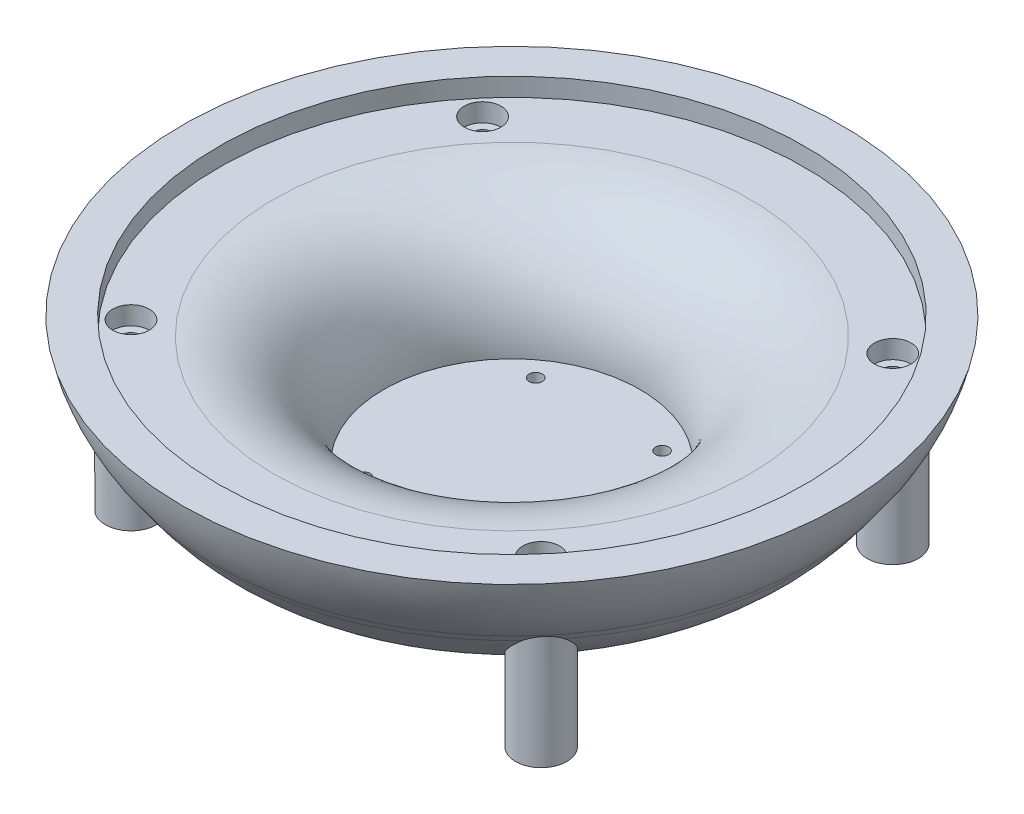
SolidWorks part; units mm, degrees
ref_plane "Front Plane" through (0, 0, 0) normal (0, 0, 1) x (1, 0, 0)
ref_plane "Top Plane" through (0, 0, 0) normal (0, 1, 0) x (1, 0, 0)
ref_plane "Right Plane" through (0, 0, 0) normal (1, 0, 0) x (0, 0, -1)
sketch "Sketch3" plane through (0, 0, 0) normal (0, 1, 0) x (1, 0, 0)
  circle A0 centre (0, 0) radius 90
extrude "Boss-Extrude2" add sketch "Sketch3" along normal blind 10
sketch "Sketch4" plane through (0, 10, 0) normal (0, 1, 0) x (1, 0, 0)
  circle A0 centre (0, 0) radius 80
extrude "Cut-Extrude1" cut sketch "Sketch4" against normal blind 5
sketch "Sketch14" plane through (0, 0, 0) normal (0, -1, 0) x (1, 0, 0)
  circle A0 centre (56, 48) radius 7
extrude "Boss-Extrude6" add sketch "Sketch14" along normal blind 40
sketch "Sketch15" plane through (0, 5, 0) normal (0, 1, 0) x (1, 0, 0)
  circle A0 centre (56, -48) radius 5
  point P2 (0, 0)
extrude "Cut-Extrude4" cut sketch "Sketch15" against normal blind 5
sketch "Sketch16" plane through (0, -40, 0) normal (0, -1, 0) x (1, 0, 0)
  circle A0 centre (56, 48) radius 4
extrude "Cut-Extrude5" cut sketch "Sketch16" against normal blind 32
sketch "Sketch17" plane through (0, -8, 0) normal (0, -1, 0) x (1, 0, 0)
  circle A0 centre (56, 48) radius 2.8
extrude "Cut-Extrude6" cut sketch "Sketch17" against normal through all
sketch "Sketch20" plane through (0, 0, 0) normal (0, -1, 0) x (1, 0, 0)
  circle A0 centre (56, -48) radius 7.0017
extrude "Boss-Extrude7" add sketch "Sketch20" along normal blind 40
sketch "Sketch22" plane through (0, -40, 0) normal (0, -1, 0) x (1, 0, 0)
  circle A0 centre (56, -48) radius 3.75
extrude "Cut-Extrude8" cut sketch "Sketch22" against normal blind 32
sketch "Sketch23" plane through (0, -8, 0) normal (0, -1, 0) x (1, 0, 0)
  circle A0 centre (56, -48) radius 2.75
extrude "Cut-Extrude9" cut sketch "Sketch23" against normal through all
sketch "Sketch24" plane through (0, 0, 0) normal (0, -1, 0) x (1, 0, 0)
  circle A0 centre (-56, 48) radius 7
extrude "Boss-Extrude8" add sketch "Sketch24" along normal blind 40
sketch "Sketch25" plane through (0, 5, 0) normal (0, 1, 0) x (1, 0, 0)
  circle A0 centre (-56, -48) radius 5
extrude "Cut-Extrude10" cut sketch "Sketch25" against normal blind 5
sketch "Sketch26" plane through (0, -40, 0) normal (0, -1, 0) x (1, 0, 0)
  circle A0 centre (-56, 48) radius 3.75
extrude "Cut-Extrude11" cut sketch "Sketch26" against normal blind 32
sketch "Sketch27" plane through (0, -8, 0) normal (0, -1, 0) x (1, 0, 0)
  circle A0 centre (-56, 48) radius 2.75
extrude "Cut-Extrude12" cut sketch "Sketch27" against normal through all
sketch "Sketch28" plane through (0, 0, 0) normal (0, -1, 0) x (1, 0, 0)
  circle A0 centre (-56, -48) radius 7
extrude "Boss-Extrude9" add sketch "Sketch28" along normal blind 40
sketch "Sketch29" plane through (0, 5, 0) normal (0, 1, 0) x (1, 0, 0)
  circle A0 centre (-56, 48) radius 5
extrude "Cut-Extrude13" cut sketch "Sketch29" against normal blind 5
sketch "Sketch30" plane through (0, -40, 0) normal (0, -1, 0) x (-1, 0, 0)
  circle A0 centre (56, 48) radius 3.75
extrude "Cut-Extrude14" cut sketch "Sketch30" against normal blind 32
sketch "Sketch31" plane through (0, -8, 0) normal (0, -1, 0) x (1, 0, 0)
  circle A0 centre (-56, -48) radius 2.75
extrude "Cut-Extrude15" cut sketch "Sketch31" against normal through all
sketch "Sketch32" plane through (0, 5, 0) normal (0, 1, 0) x (1, 0, 0)
  circle A0 centre (56, 48) radius 5
extrude "Cut-Extrude16" cut sketch "Sketch32" against normal blind 5
sketch "Sketch35" plane through (0, 0, 0) normal (0, -1, 0) x (1, 0, 0)
  circle A0 centre (0, 0) radius 85
extrude "Boss-Extrude11" add sketch "Sketch35" along normal blind 30
sketch "Sketch38" plane through (0, 5, 0) normal (0, 1, 0) x (1, 0, 0)
  circle A0 centre (0, 0) radius 35
extrude "Cut-Extrude18" cut sketch "Sketch38" against normal blind 30
sketch "Sketch39" plane through (0, -25, 0) normal (0, 1, 0) x (1, 0, 0)
  circle A0 centre (17.5, 23.5) radius 1.8
extrude "Cut-Extrude19" cut sketch "Sketch39" against normal through all
sketch "Sketch40" plane through (0, -25, 0) normal (0, 1, 0) x (1, 0, 0)
  circle A0 centre (17.5, -23.5) radius 1.8
extrude "Cut-Extrude20" cut sketch "Sketch40" against normal through all
sketch "Sketch41" plane through (0, -30, 0) normal (0, -1, 0) x (1, 0, 0)
  circle A0 centre (-17, 23.5) radius 1.8
extrude "Cut-Extrude21" cut sketch "Sketch41" against normal through all
sketch "Sketch43" plane through (0, -30, 0) normal (0, -1, 0) x (1, 0, 0)
  circle A0 centre (-17, -23.5) radius 1.8
extrude "Cut-Extrude22" cut sketch "Sketch43" against normal through all
fillet "Fillet12" radius 45 1 edges at (0, -30, -85)
fillet "Fillet13" radius 45 1 edges at (0, 0, 85)
fillet "Fillet14" radius 45 1 edges at (0, 0, 90)
fillet "Fillet15" radius 30 1 edges at (0, 5, 35)
sketch "Sketch44" plane through (0, -30, 0) normal (0, -1, 0) x (1, 0, 0)
  circle A0 centre (-56, 48) radius 3.75
extrude "Cut-Extrude23" cut sketch "Sketch44" against normal blind 27
sketch "Sketch45" plane through (0, -3, 0) normal (0, -1, 0) x (1, 0, 0)
  circle A0 centre (-56, 48) radius 2.75
extrude "Cut-Extrude24" cut sketch "Sketch45" against normal through all
sketch "Sketch46" plane through (0, -30, 0) normal (0, -1, 0) x (1, 0, 0)
  circle A0 centre (-56, -48) radius 3.75
extrude "Cut-Extrude25" cut sketch "Sketch46" against normal blind 27
sketch "Sketch47" plane through (0, -3, 0) normal (0, -1, 0) x (1, 0, 0)
  circle A0 centre (-56, -48) radius 2.75
extrude "Cut-Extrude26" cut sketch "Sketch47" against normal through all
sketch "Sketch49" plane through (0, -30, 0) normal (0, -1, 0) x (1, 0, 0)
  circle A0 centre (56, 48) radius 3.75
extrude "Cut-Extrude28" cut sketch "Sketch49" against normal blind 27
sketch "Sketch50" plane through (0, -3, 0) normal (0, -1, 0) x (1, 0, 0)
  circle A0 centre (56, 48) radius 2.75
extrude "Cut-Extrude29" cut sketch "Sketch50" against normal through all
sketch "Sketch51" plane through (0, -30, 0) normal (0, -1, 0) x (1, 0, 0)
  circle A0 centre (56, -48) radius 3.75
extrude "Cut-Extrude30" cut sketch "Sketch51" against normal blind 27
sketch "Sketch52" plane through (0, -3, 0) normal (0, -1, 0) x (1, 0, 0)
  circle A0 centre (56, -48) radius 2.75
extrude "Cut-Extrude31" cut sketch "Sketch52" against normal blind 27
